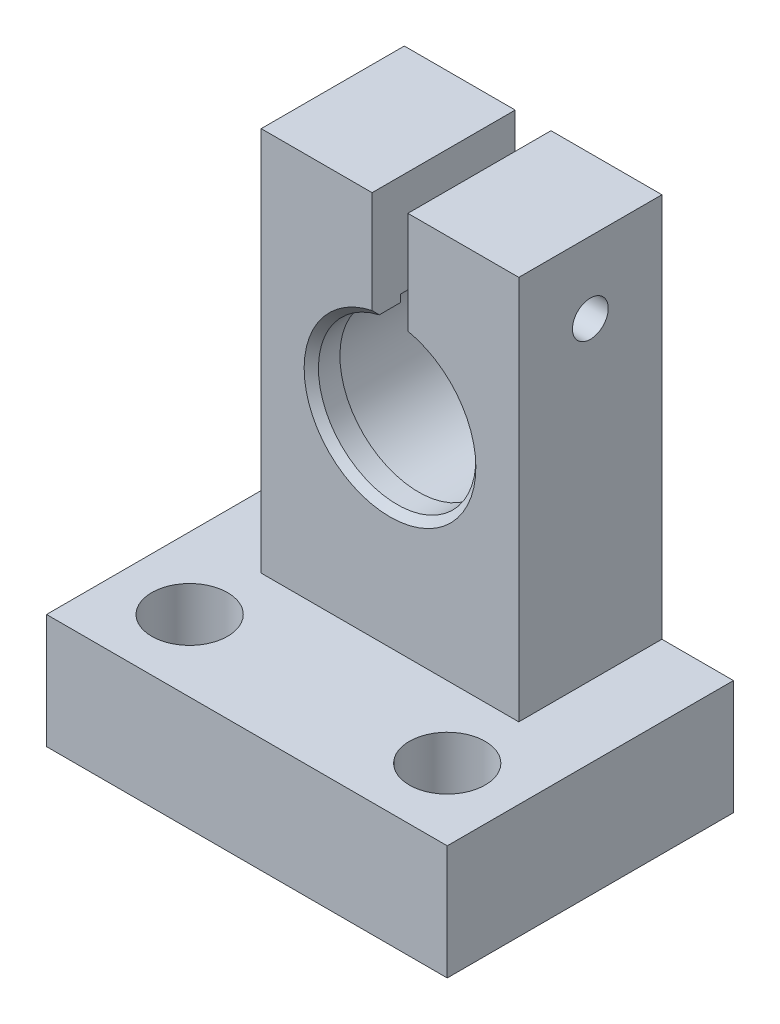
SolidWorks part; units mm, degrees
material "AISI 1045 Steel, cold drawn"
ref_plane "Front Plane" through (0, 0, 0) normal (0, 0, 1) x (1, 0, 0)
ref_plane "Top Plane" through (0, 0, 0) normal (0, 1, 0) x (1, 0, 0)
ref_plane "Right Plane" through (0, 0, 0) normal (1, 0, 0) x (0, 0, -1)
sketch "Sketch1" plane through (0, 0, 0) normal (0, 0, 1) x (1, 0, 0)
  line L1 (9, -21.9) -> (-9, -21.9)
  line L2 (9, -21.9) -> (9, 13)
  line L3 (9, 13) -> (-9, 13)
  line L4 (-9, -21.9) -> (-9, 13)
  line L5 (9, -21.9) -> (-9, 13) construction
  line L6 (9, 13) -> (-9, -21.9) construction
  circle A0 centre (0, 0) radius 6
  point P3 (0, -4.45)
  dimension "D1" = 12
  dimension "D2" = 13
  dimension "D3" = 21.9
  dimension "D4" = 18
extrude "Boss-Extrude1" add sketch "Sketch1" along normal blind 10
sketch "Sketch2" plane through (0, 0, 10) normal (0, 0, -1) x (-1, 0, 0)
  circle A0 centre (0, 0) radius 6 construction
  circle A1 centre (0, 0) radius 6
  circle A2 centre (0, 0) radius 5.5
  dimension "D1" = 0.5
extrude "Boss-Extrude2" add sketch "Sketch2" along normal blind 2
sketch "Sketch3" plane through (0, 0, 10) normal (0, 0, 1) x (1, 0, 0)
  line L0 (9, 13) -> (-9, 13) construction
  line L1 (1.25, 5.3561) -> (-1.25, 5.3561)
  line L2 (1.25, 5.3561) -> (1.25, 13)
  line L3 (1.25, 13) -> (-1.25, 13)
  line L4 (-1.25, 5.3561) -> (-1.25, 13)
  line L5 (1.25, 5.3561) -> (-1.25, 13) construction
  line L6 (1.25, 13) -> (-1.25, 5.3561) construction
  circle A0 centre (0, 0) radius 5.5 construction
  point P0 (0, 9.178)
  dimension "D1" = 2.5
extrude "Cut-Extrude1" cut sketch "Sketch3" against normal through all
hole_wizard "CBORE for M3 SHCS1" positions "Sketch4" profile "Sketch5" counterbore size "M3" standard "ANSI Metric" end condition up to next
sketch "Sketch4" plane through (9, 0, 0) normal (1, 0, 0) x (0, 0, -1)
  line L0 (0, -21.9) -> (0, 13) construction
  line L1 (-10, 13) -> (0, 13) construction
  point P0 (-5, 8)
  dimension "D1" = 5
  dimension "D2" = 5
sketch "Sketch5" plane through (9, 8, 5) normal (0, 1, 0) x (0, 0, -1)
  line L0 (0, 0) -> (0, 7.75)
  line L1 (0, 7.75) -> (1.6, 7.75)
  line L3 (1.6, 7.75) -> (1.6, 3)
  line L4 (1.6, 3) -> (3.25, 3)
  line L5 (3.25, 3) -> (3.25, 0)
  line L7 (3.25, 0) -> (0, 0)
  line L11 (0, -6.35) -> (0, 107.95) construction
  dimension "Thru Hole Dia." = 3.2
  dimension "Thru Hole Depth" = 7.75
  dimension "C'Bore Dia." = 6.5
  dimension "C'Bore Depth" = 3
hole_wizard "Tap Drill for M3x0.5 Tap1" positions "Sketch6" profile "Sketch7" hole size "M3x0.5" standard "ANSI Metric" end condition up to next
sketch "Sketch6" plane through (-9, 0, 0) normal (-1, 0, 0) x (0, 0, 1)
  line L0 (10, 13) -> (10, -21.9) construction
  line L1 (10, 13) -> (0, 13) construction
  point P0 (5, 8)
  dimension "D1" = 5
  dimension "D2" = 5
sketch "Sketch7" plane through (-9, 8, 5) normal (0, 1, 0) x (0, 0, 1)
  line L0 (0, 0) -> (0, 7.75)
  line L1 (0, 7.75) -> (1.25, 7.75)
  line L2 (1.25, 7.75) -> (1.25, 0)
  line L5 (1.25, 0) -> (0, 0)
  line L11 (0, -6.35) -> (0, 107.95) construction
  dimension "Thru Hole Dia." = 2.5
  dimension "Thru Hole Depth" = 7.75
chamfer "Chamfer1" distance 0.5 angle 45 2 edges at (0, -5.5, 10) (0, -6, 0)
sketch "Sketch11" plane through (-9, 0, 0) normal (-1, 0, 0) x (0, 0, 1)
  line L0 (0, 13) -> (0, -21.9) construction
  line L1 (0, -21.9) -> (10, -21.9)
  line L2 (0, -21.9) -> (0, -13.9)
  line L3 (0, -13.9) -> (10, -13.9)
  line L4 (10, -21.9) -> (10, -13.9)
  line L5 (10, 13) -> (10, -21.9) construction
  dimension "D1" = 8
extrude "Boss-Extrude4" add sketch "Sketch11" along normal blind 5
mirror "Mirror1" about plane through (0, 0, 0) normal (1, 0, 0) of "Boss-Extrude4"
sketch "Sketch8" plane through (0, -21.9, 0) normal (0, -1, 0) x (1, 0, 0)
  line L0 (-14, 0) -> (-14, 10) construction
  line L1 (-14, 10) -> (14, 10)
  line L2 (-14, 10) -> (-14, 20)
  line L3 (-14, 20) -> (14, 20)
  line L4 (14, 10) -> (14, 20)
  dimension "D1" = 10
extrude "Boss-Extrude3" add sketch "Sketch8" against normal up to surface (8 mm away) up to face at (-11.5, -13.9, 5)
hole_wizard "M5 Clearance Hole1" positions "Sketch9" profile "Sketch10" hole size "M5" standard "ANSI Metric" end condition up to next
sketch "Sketch9" plane through (0, -13.9, 0) normal (0, 1, 0) x (1, 0, 0)
  line L0 (14, -20) -> (-14, -20) construction
  line L1 (-14, -20) -> (-14, 0) construction
  line L2 (0, -10) -> (0, -20) construction
  line L4 (-9, -10) -> (9, -10) construction
  point P0 (-9, -15)
  point P14 (9, -15)
  dimension "D1" = 5
  dimension "D2" = 5
sketch "Sketch10" plane through (-9, -13.9, 15) normal (1, 0, 0) x (0, 0, 1)
  line L0 (0, 0) -> (0, 8)
  line L1 (0, 8) -> (2.65, 8)
  line L2 (2.65, 8) -> (2.65, 0)
  line L5 (2.65, 0) -> (0, 0)
  line L11 (0, -6.35) -> (0, 107.95) construction
  dimension "Thru Hole Dia." = 5.3
  dimension "Thru Hole Depth" = 8
mirror "Mirror2" about plane through (14, 0, 0) normal (-1, 0, 0) of bodies 107
delete or keep bodies "Body-Delete/Keep 1" type delete bodies bodies 107
